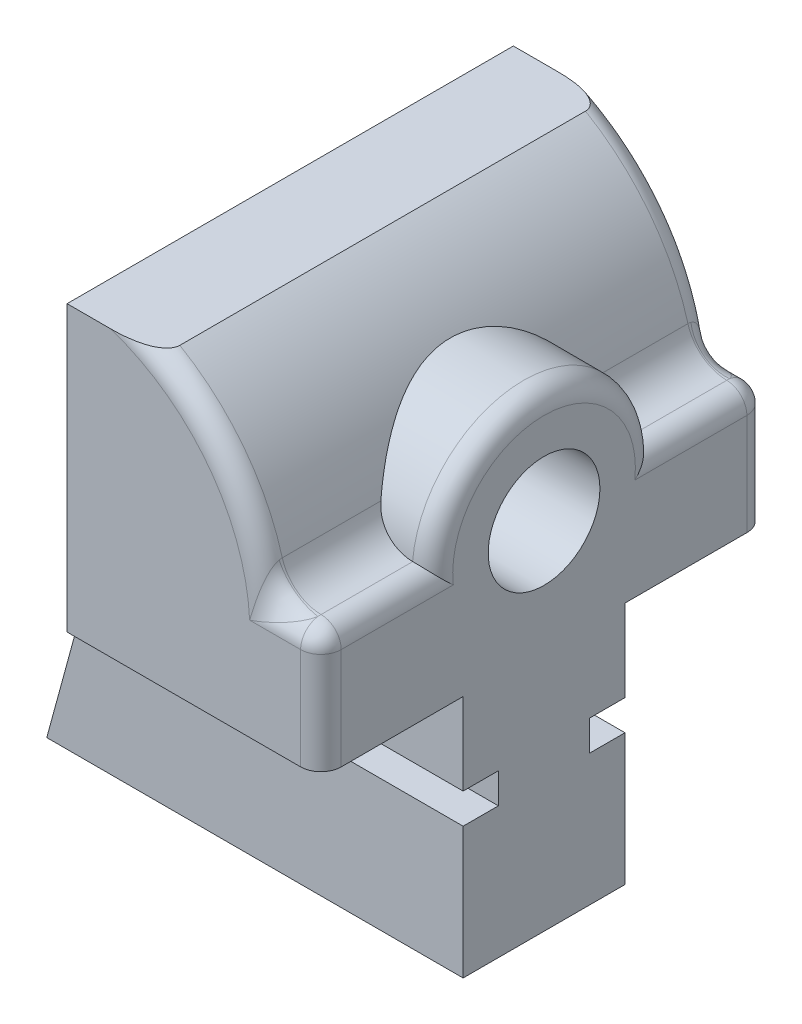
SolidWorks part; units mm, degrees
ref_plane "Front" through (0, 0, 0) normal (0, 0, 1) x (1, 0, 0)
ref_plane "Top" through (0, 0, 0) normal (0, 1, 0) x (1, 0, 0)
ref_plane "Right" through (0, 0, 0) normal (1, 0, 0) x (0, 0, -1)
sketch "Sketch1" plane through (0, 0, 0) normal (0, 0, 1) x (1, 0, 0)
  line L0 (0, 0) -> (0, 44.45)
  line L2 (31.4255, 19.05) -> (39.6748, 19.05)
  line L3 (39.6748, 19.05) -> (39.6748, 0)
  line L4 (39.6748, 0) -> (0, 0)
  line L5 (0, 44.45) -> (14.453, 44.45)
  arc A0 (14.453, 44.45) -> (31.4255, 19.05) centre (-3.175, 14.3002) cw
  dimension "D2" = 34.925
  dimension "D1" = 39.6748
  dimension "D3" = 3.175
  dimension "D4" = 30.1498
  dimension "D5" = 44.45
  dimension "D6" = 19.05
extrude "Boss-Extrude1" add sketch "Sketch1" along normal blind 69.7484
sketch "Sketch2" plane through (39.6748, 0, 0) normal (1, 0, 0) x (0, 0, -1)
  line L0 (-47.5234, -17.5514) -> (-47.5234, -38.1)
  line L1 (-69.7484, 0) -> (0, 0) construction
  line L2 (-47.5234, 0) -> (-22.225, 0)
  line L3 (-47.5234, 0) -> (-47.5234, -12.8016)
  line L4 (-47.5234, -38.1) -> (-22.225, -38.1)
  line L5 (-22.225, 0) -> (-22.225, -12.8016)
  line L6 (-22.225, -17.5514) -> (-22.225, -38.1)
  line L7 (-22.225, -12.8016) -> (-27.7368, -12.8016)
  line L9 (-22.225, -17.5514) -> (-27.7368, -17.5514)
  line L10 (-27.7368, -12.8016) -> (-27.7368, -17.5514)
  line L11 (-47.5234, -12.8016) -> (-42.0116, -12.8016)
  line L13 (-47.5234, -17.5514) -> (-42.0116, -17.5514)
  line L14 (-42.0116, -12.8016) -> (-42.0116, -17.5514)
  line L15 (-69.7484, 0) -> (0, 0) construction
  point P15 (-34.8742, 0)
  dimension "D1" = 5.5118
  dimension "D2" = 4.7498
  dimension "D3" = 38.1
  dimension "D4" = 12.8016
  dimension "D5" = 25.2984
extrude "Boss-Extrude2" add sketch "Sketch2" against normal blind 65.0748
sketch "Sketch3" plane through (0, 0, 47.5234) normal (0, 0, 1) x (1, 0, 0)
  line L0 (-25.4, -38.1) -> (-15.875, -3.175)
  line L1 (-15.875, -3.175) -> (-5.4993, -3.175)
  line L2 (0, 44.45) -> (0, 0) construction
  line L3 (0, 44.45) -> (0, 0) construction
  line L5 (-25.4, 0) -> (0, 0) construction
  line L6 (-25.4, 0) -> (0, 0)
  line L7 (-25.4, 0) -> (-25.4, -12.8016) construction
  line L8 (-25.4, 0) -> (-25.4, -12.8016)
  line L9 (-25.4, -17.5514) -> (-25.4, -38.1) construction
  line L10 (-25.4, -12.8016) -> (-25.4, -38.1)
  arc A0 (0, 0) -> (-5.4993, -3.175) centre (-5.4993, 3.175) cw
  dimension "D1" = 6.35
  dimension "D2" = 9.525
  dimension "D3" = 34.925
extrude "Cut-Extrude1" cut sketch "Sketch3" against normal up to next
sketch "Sketch4" plane through (39.6748, 0, 0) normal (1, 0, 0) x (0, 0, -1)
  line L0 (-47.5234, -38.1) -> (-22.225, -38.1) construction
  line L1 (-69.7484, 19.05) -> (0, 19.05) construction
  line L2 (-52.2505, 19.05) -> (-17.4979, 19.05)
  arc A0 (-17.4979, 19.05) -> (-52.2505, 19.05) centre (-34.8742, 17.4498) ccw
  point P4 (-34.8742, -38.1)
  dimension "D2" = 34.8996
  dimension "D1" = 55.5498
extrude "Boss-Extrude3" add sketch "Sketch4" against normal up to surface (8.2493 mm away) up to face at (24.4014, 32.7271, 34.8742)
hole_wizard "3/4-16 Tapped Hole1" positions "Sketch5" profile "Sketch6" tap size "3/4-16" standard "ANSI Inch"
sketch "Sketch5" plane through (39.6748, 0, 0) normal (1, 0, 0) x (0, 0, -1)
  arc A4 (-17.4979, 19.05) -> (-52.2505, 19.05) centre (-34.8742, 17.4498) ccw construction
  point P0 (-34.8742, 17.4498)
cosmetic thread "Hole Thread1" parameters "D1"=38.1, "D2"=19.05
sketch "Sketch6" plane through (39.6748, 17.4498, 34.8742) normal (0, 1, 0) x (0, 0, -1)
  line L0 (0, 0) -> (0, 35.3961)
  line L1 (0, 35.3961) -> (8.7312, 30.1498)
  line L2 (8.7312, 30.1498) -> (8.7312, 0)
  line L5 (8.7312, 0) -> (0, 0)
  line L10 (0, 35.3961) -> (-8.7313, 30.1498) construction
  line L11 (0, -6.35) -> (0, 107.95) construction
  dimension "Tap Drill Dia." = 17.4625
  dimension "Tap Drill Depth" = 30.1498
  dimension "Drill Angle" = 118
hole_wizard "1/4-20 Tapped Hole1" positions "Sketch7" profile "Sketch8" tap size "1/4-20" standard "ANSI Inch"
sketch "Sketch7" plane through (0, 0, 0) normal (-1, 0, 0) x (0, 0, 1)
  line L0 (0, 44.45) -> (0, 0) construction
  line L1 (69.7484, 0) -> (47.5234, 0) construction
  point P0 (15.875, 25.4)
  point P2 (53.975, 25.4)
  dimension "D1" = 15.875
  dimension "D2" = 38.1
  dimension "D3" = 25.4
sketch "Sketch8" plane through (0, 25.4, 15.875) normal (0, 1, 0) x (0, 0, 1)
  line L0 (0, 0) -> (0, 17.4088)
  line L1 (0, 17.4088) -> (2.5527, 15.875)
  line L2 (2.5527, 15.875) -> (2.5527, 0)
  line L5 (2.5527, 0) -> (0, 0)
  line L10 (0, 17.4088) -> (-2.5527, 15.875) construction
  line L11 (0, -6.35) -> (0, 107.95) construction
  dimension "Tap Drill Dia." = 5.1054
  dimension "Tap Drill Depth" = 15.875
  dimension "Drill Angle" = 118
cosmetic thread "Hole Thread2" parameters "D1"=12.7, "D2"=6.35
cosmetic thread "Hole Thread3" parameters "D1"=12.7, "D2"=6.35
fillet "Fillet1" radius 3.175 9 edges at (25.8637, 33.7041, 69.7484) (25.8637, 33.7041, 0) (39.6748, 34.8996, 34.8742) (39.6748, 9.525, 69.7484) (39.6748, 9.525, 0) (39.6748, 19.05, 8.749) (39.6748, 19.05, 60.9994) (35.5502, 19.05, 69.7484) (35.5502, 19.05, 0)
fillet "Fillet2" radius 6.35 4 edges at (31.4255, 19.05, 59.4119) (31.4255, 19.05, 10.3365) (31.036, 18.6059, 68.1929) (31.036, 18.6059, 1.5555)
hole_wizard "#12-24 Tapped Hole1" positions "Sketch9" profile "Sketch10" tap size "#12-24" standard "ANSI Inch"
sketch "Sketch9" plane through (0, -38.1, 0) normal (0, -1, 0) x (-1, 0, 0)
  line L0 (-39.6748, -47.5234) -> (-39.6748, -22.225) construction
  line L1 (25.4, -22.225) -> (-39.6748, -22.225) construction
  point P0 (-9.525, -26.9367)
  point P2 (-9.525, -42.8117)
  dimension "D1" = 30.1498
  dimension "D2" = 15.875
  dimension "D3" = 4.7117
sketch "Sketch10" plane through (9.525, -38.1, 26.9367) normal (1, 0, 0) x (0, 0, -1)
  line L0 (0, 0) -> (0, 20.4007)
  line L1 (0, 20.4007) -> (2.2479, 19.05)
  line L2 (2.2479, 19.05) -> (2.2479, 9.525)
  line L3 (2.2479, 9.525) -> (2.7432, 9.525)
  line L4 (2.7432, 9.525) -> (2.7432, 0)
  line L5 (2.7432, 0) -> (0, 0)
  line L10 (0, 20.4007) -> (-2.2479, 19.05) construction
  line L11 (0, -6.35) -> (0, 107.95) construction
  dimension "Tap Drill Dia." = 4.4958
  dimension "Tap Drill Depth" = 19.05
  dimension "Thread Major Dia." = 5.4864
  dimension "Thread Depth" = 9.525
  dimension "Drill Angle" = 118
ref_axis "Axis1" through (9.525, 17.4498, 34.8742) along (1, 0, 0)
